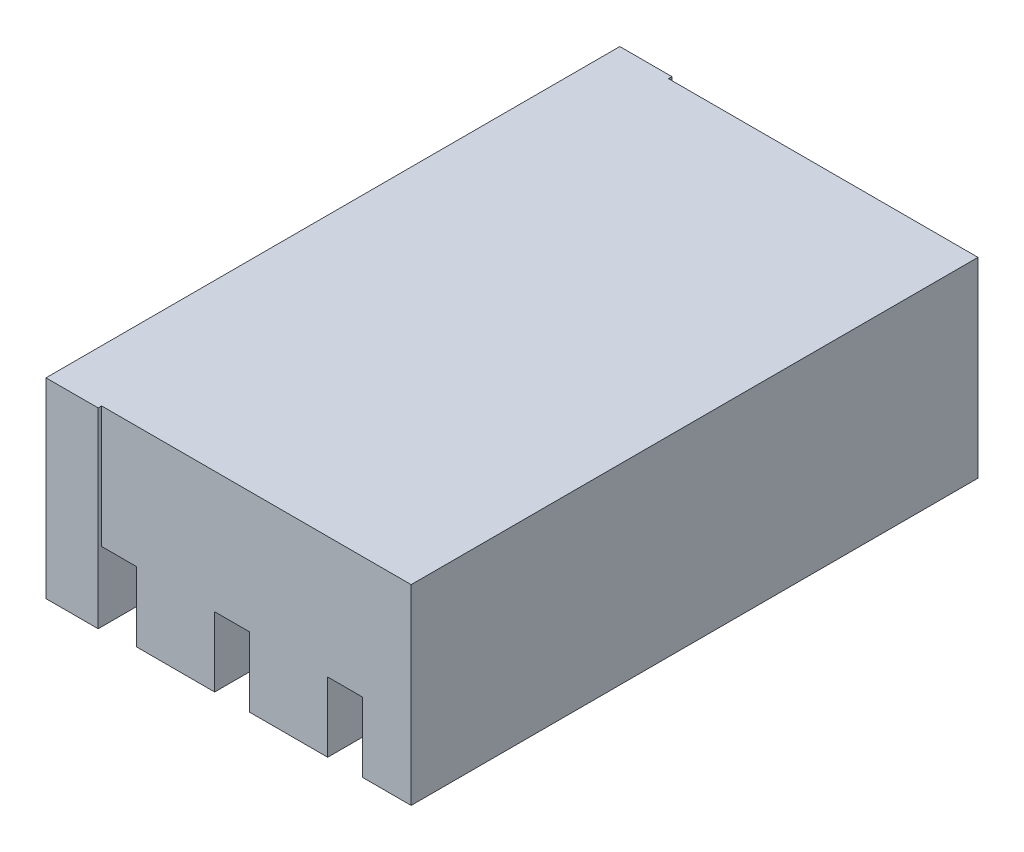
SolidWorks part; units mm, degrees
ref_plane "Front Plane" through (0, 0, 0) normal (0, 0, 1) x (1, 0, 0)
ref_plane "Top Plane" through (0, 0, 0) normal (0, 1, 0) x (1, 0, 0)
ref_plane "Right Plane" through (0, 0, 0) normal (1, 0, 0) x (0, 0, -1)
sketch "Sketch1" plane through (0, 0, 0) normal (0, 1, 0) x (1, 0, 0)
  line L0 (7.5, 15) -> (10.5, 15)
  line L1 (7.5, 15) -> (-7.5, 15)
  line L2 (7.5, 15) -> (7.5, -15)
  line L3 (7.5, -15) -> (-7.5, -15)
  line L4 (-7.5, 15) -> (-7.5, -15)
  line L5 (7.5, 15) -> (-7.5, -15) construction
  line L6 (7.5, -15) -> (-7.5, 15) construction
  line L7 (10.5, 18) -> (-10.5, 18)
  line L8 (10.5, 18) -> (10.5, -18)
  line L9 (10.5, -18) -> (-10.5, -18)
  line L10 (-10.5, 18) -> (-10.5, -18)
  line L11 (10.5, 18) -> (-10.5, -18) construction
  line L12 (10.5, -18) -> (-10.5, 18) construction
  line L13 (-7.5, 15) -> (-10.5, 15)
  point P0 (0, 0)
  point P6 (0, 0)
  dimension "D1" = 15
  dimension "D2" = 30
  dimension "D3" = 3
  dimension "D4" = 3
extrude "Boss-Extrude1" add sketch "Sketch1" along normal blind 11 contours L4 L13 L10 L9 L8 L0 L2 L3 region at (9, 0, -14.6088)
sketch "Sketch2" plane through (0, 11, 0) normal (0, 1, 0) x (1, 0, 0)
  line L1 (10.5, -18) -> (-10.5, -18)
  line L2 (10.5, -18) -> (10.5, 15)
  line L3 (10.5, 15) -> (-10.5, 15)
  line L4 (-10.5, -18) -> (-10.5, 15)
extrude "Boss-Extrude2" add sketch "Sketch2" against normal blind 3
sketch "Sketch3" plane through (0, 0, 0) normal (0, -1, 0) x (1, 0, 0)
  line L0 (7.5, 15) -> (-7.5, 15) construction
  line L1 (-7.5, 15) -> (-5.5, 15)
  line L2 (-7.5, 15) -> (-7.5, 19.6646)
  line L3 (-7.5, 19.6646) -> (-5.5, 19.6646)
  line L4 (-5.5, 15) -> (-5.5, 19.6646)
  line L5 (1, 23.3856) -> (-1, 23.3856)
  line L6 (1, 23.3856) -> (1, 15)
  line L7 (1, 15) -> (-1, 15)
  line L8 (-1, 23.3856) -> (-1, 15)
  line L9 (1, 23.3856) -> (-1, 15) construction
  line L10 (1, 15) -> (-1, 23.3856) construction
  line L12 (7.5, 15) -> (5.5, 15)
  line L13 (7.5, 15) -> (7.5, 20.0915)
  line L14 (7.5, 20.0915) -> (5.5, 20.0915)
  line L15 (5.5, 15) -> (5.5, 20.0915)
  point P5 (0, 19.1928)
  dimension "D1" = 2
  dimension "D2" = 2
  dimension "D3" = 2
extrude "Cut-Extrude1" cut sketch "Sketch3" against normal blind 4
sketch "Sketch4" plane through (0, 0, 0) normal (0, -1, 0) x (1, 0, 0)
  line L0 (7.5, 15) -> (-7.5, 15) construction
  line L1 (10.5, 18) -> (7.5, 18) construction
  line L2 (5.5, 18) -> (7.5, 18) construction
  line L3 (5.5, 18) -> (1, 18) construction
  line L4 (1, 18) -> (-1, 18) construction
  line L5 (-1, 18) -> (-5.5, 18) construction
  line L6 (-5.5, 18) -> (-7.5, 18) construction
  line L7 (-7.5, 18) -> (-10.5, 18) construction
  line L8 (-10.5, -15) -> (-10.5, 18) construction
  line L9 (-7.5, -15) -> (-10.5, -15) construction
  line L10 (-7.5, -15) -> (-7.5, 15) construction
  line L11 (7.5, -15) -> (7.5, 15) construction
  line L12 (7.5, -15) -> (10.5, -15) construction
  line L13 (10.5, -15) -> (10.5, 18) construction
  line L14 (7.5, 15) -> (-7.5, 15) construction
  line L15 (10.5, 18) -> (7.5, 18) construction
  line L16 (5.5, 18) -> (7.5, 18) construction
  line L17 (5.5, 18) -> (1, 18) construction
  line L18 (1, 18) -> (-1, 18) construction
  line L19 (-1, 18) -> (-5.5, 18) construction
  line L20 (-5.5, 18) -> (-7.5, 18) construction
  line L21 (-7.5, 18) -> (-10.5, 18) construction
  line L22 (-10.5, -15) -> (-10.5, 18) construction
  line L23 (-7.5, -15) -> (-10.5, -15) construction
  line L24 (-7.5, -15) -> (-7.5, 15) construction
  line L25 (7.5, -15) -> (7.5, 15) construction
  line L26 (7.5, -15) -> (10.5, -15) construction
  line L27 (10.5, -15) -> (10.5, 18) construction
  line L28 (7.7, 15.2) -> (-7.7, 15.2)
  line L29 (-7.7, -14.8) -> (-7.7, 15.2)
  line L30 (-7.7, -14.8) -> (-10.3, -14.8)
  line L31 (-10.3, -14.8) -> (-10.3, 17.8)
  line L32 (-7.5, 17.8) -> (-10.3, 17.8)
  line L33 (-5.5, 17.8) -> (-7.5, 17.8)
  line L34 (-1, 17.8) -> (-5.5, 17.8)
  line L35 (1, 17.8) -> (-1, 17.8)
  line L36 (5.5, 17.8) -> (1, 17.8)
  line L37 (5.5, 17.8) -> (7.5, 17.8)
  line L38 (10.3, 17.8) -> (7.5, 17.8)
  line L39 (10.3, -14.8) -> (10.3, 17.8)
  line L40 (7.7, -14.8) -> (10.3, -14.8)
  line L41 (7.7, -14.8) -> (7.7, 15.2)
  line L42 (-7.7, -14.8) -> (7.7, -14.8)
  line L43 (21.7154, 27.8258) -> (-21.7154, 27.8258)
  line L44 (21.7154, 27.8258) -> (21.7154, -27.8258)
  line L45 (21.7154, -27.8258) -> (-21.7154, -27.8258)
  line L46 (-21.7154, 27.8258) -> (-21.7154, -27.8258)
  line L47 (21.7154, 27.8258) -> (-21.7154, -27.8258) construction
  line L48 (21.7154, -27.8258) -> (-21.7154, 27.8258) construction
  point P28 (0, 0)
  line M29 (-7.5, -15) -> (-7.5, 18)
  line M30 (-7.5, 18) -> (-10.5, 18)
  line M31 (-10.5, 18) -> (-10.5, -15)
  line M32 (-10.5, -15) -> (-7.5, -15)
  dimension "D1" = 0.2
extrude "Cut-Extrude2" cut sketch "Sketch4" against normal up to surface (8 mm away) contours L42 L41 L28 M29 region at (0.1, 0, 0.2) up to face at (0, 8, 0)
extrude "Cut-Extrude3" cut sketch "Sketch4<3>" against normal through all both and the other way through all contours L43 L46 L45 L44 L42 L33 L34 L35 L36 L37 L38 L39 L40 M29 M32 M31 M30 region at (21.0095, 0, 0)
sketch "Sketch4<3>" plane through (0, 0, 0) normal (0, -1, 0) x (1, 0, 0) same geometry as "Sketch4"
